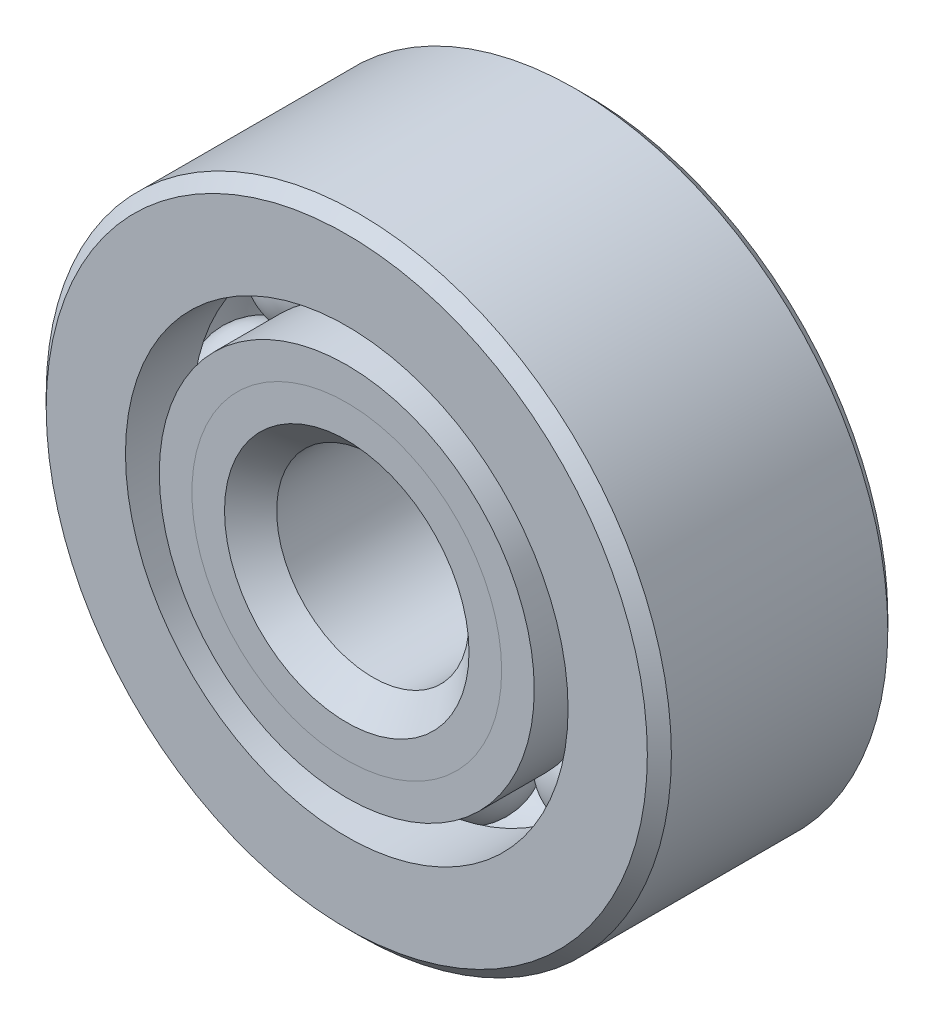
SolidWorks part; units mm, degrees
ref_plane "Front Plane" through (0, 0, 0) normal (0, 0, 1) x (1, 0, 0)
ref_plane "Top Plane" through (0, 0, 0) normal (0, 1, 0) x (1, 0, 0)
ref_plane "Right Plane" through (0, 0, 0) normal (1, 0, 0) x (0, 0, -1)
sketch "Sketch1" plane through (0, 0, 0) normal (1, 0, 0) x (0, 0, -1)
  line L0 (-2.5, 0) -> (2.5, 0) construction
  line L1 (0, 6.5) -> (0, -6.5) construction
  line L2 (2.25, 6.5) -> (-2.25, 6.5)
  line L3 (-2.25, 6.5) -> (-2.5, 6.25)
  line L4 (-2.5, 6.25) -> (-2.5, 4.6016)
  line L5 (-2.5, 4.6016) -> (-1.1111, 4.6016)
  line L6 (2.5, 4.6016) -> (1.1111, 4.6016)
  line L7 (2.5, 6.25) -> (2.5, 4.6016)
  line L8 (2.25, 6.5) -> (2.5, 6.25)
  line L9 (0, 6.5) -> (0, 4.25) construction
  line L10 (0, 4.25) -> (0, 2) construction
  arc A0 (-1.1111, 4.6016) -> (1.1111, 4.6016) centre (0, 4.25) cw
  point P14 (0, 2)
  dimension "D3" = 2.2222
  dimension "D1" = 45
  dimension "Width" = 5
  dimension "OD" = 13
  dimension "D2" = 0.25
  dimension "Shaft Dia" = 4
  dimension "D4" = 0.3516
revolve "Revolve1" add sketch "Sketch1" angle 360 about L0
sketch "Sketch2" plane through (0, 0, 0) normal (1, 0, 0) x (0, 0, -1)
  line L0 (-2.5, 3.8984) -> (-1.1111, 3.8984)
  line L1 (-2.5, 6.25) -> (-2.5, -6.25) construction
  line L2 (-2.5, 3.8984) -> (-2.5, 3.2203)
  line L3 (-2.5, 3.2203) -> (-1.822, 2.5423)
  line L4 (-1.822, 2.5423) -> (0, 2.5423)
  line L5 (0, 6.5) -> (0, -6.5) construction
  line L6 (0, 2.5423) -> (0, 3.0846)
  line L7 (0, 3.0846) -> (0, 2) construction
  line L8 (-2.5, 3.8984) -> (-2.5, 2.5423) construction
  line L9 (-2.5, 2.5423) -> (-1.822, 2.5423) construction
  arc A0 (-1.1111, 3.8984) -> (0, 3.0846) centre (0, 4.25) ccw
  arc A1 (1.1111, 4.6016) -> (-1.1111, 4.6016) centre (0, 4.25) ccw construction
  circle A2 centre (0, 4.25) radius 1.1654 construction
  dimension "D1" = 45
revolve "Revolve2" add sketch "Sketch2" angle 360 about L0
sketch "Sketch3" plane through (0, 0, 0) normal (1, 0, 0) x (0, 0, -1)
  line L0 (-2.5, 3.2203) -> (-1.822, 2.5423)
  line L1 (-1.822, 2.5423) -> (0, 2.5423)
  line L2 (0, 2.5423) -> (0, 3.0846)
  line L3 (-2.5, 3.2203) -> (-2.5, 2.5423)
  line L4 (-2.5, 3.8984) -> (-2.5, 2.5423) construction
  line L5 (-2.5, 2.5423) -> (-1.9577, 2)
  line L6 (-1.9577, 2) -> (2.25, 2)
  line L7 (2.25, 6.5) -> (2.25, -6.5) construction
  line L8 (2.25, 2) -> (2.5, 2.25)
  line L9 (2.5, -6.25) -> (2.5, 6.25) construction
  line L10 (2.5, 2.25) -> (2.5, 3.8984)
  line L11 (2.5, 3.8984) -> (1.1111, 3.8984)
  line L13 (2.25, 6.5) -> (2.5, 6.25) construction
  circle A0 centre (0, 4.25) radius 1.1654 construction
  arc A1 (1.1111, 3.8984) -> (0, 3.0846) centre (0, 4.25) cw
revolve "Revolve3" add sketch "Sketch3" angle 360 about L0
sketch "Sketch4" plane through (0, 0, 0) normal (1, 0, 0) x (0, 0, -1)
  line L0 (-1.1654, 4.25) -> (1.1654, 4.25)
  circle A1 centre (0, 4.25) radius 1.1654 construction
  arc A2 (-1.1654, 4.25) -> (1.1654, 4.25) centre (0, 4.25) cw
  arc A3 (1.1111, 4.6016) -> (-1.1111, 4.6016) centre (0, 4.25) ccw construction
revolve "Revolve4" add sketch "Sketch4" angle 360 about L0
ref_axis "Axis1" through (0, 0, -2.5) along (0, 0, 1)
pattern_circular "CirPattern1" count 8 every 45 about axis through (0, 0, -2.5) along (0, 0, 1) of bodies 104
equation "\"D2@Sketch1\" = \"Width@Sketch1\"*.05"
equation "\"D3@Sketch1\" = \"Width@Sketch1\"/2.25"
equation "\"D4@Sketch1\" = (((\"OD@Sketch1\"-\"Width@Sketch1\")/2)/3.25)/3.5"
equation "\"D2@CirPattern1\" = 360/\"Balls@CirPattern1\""
